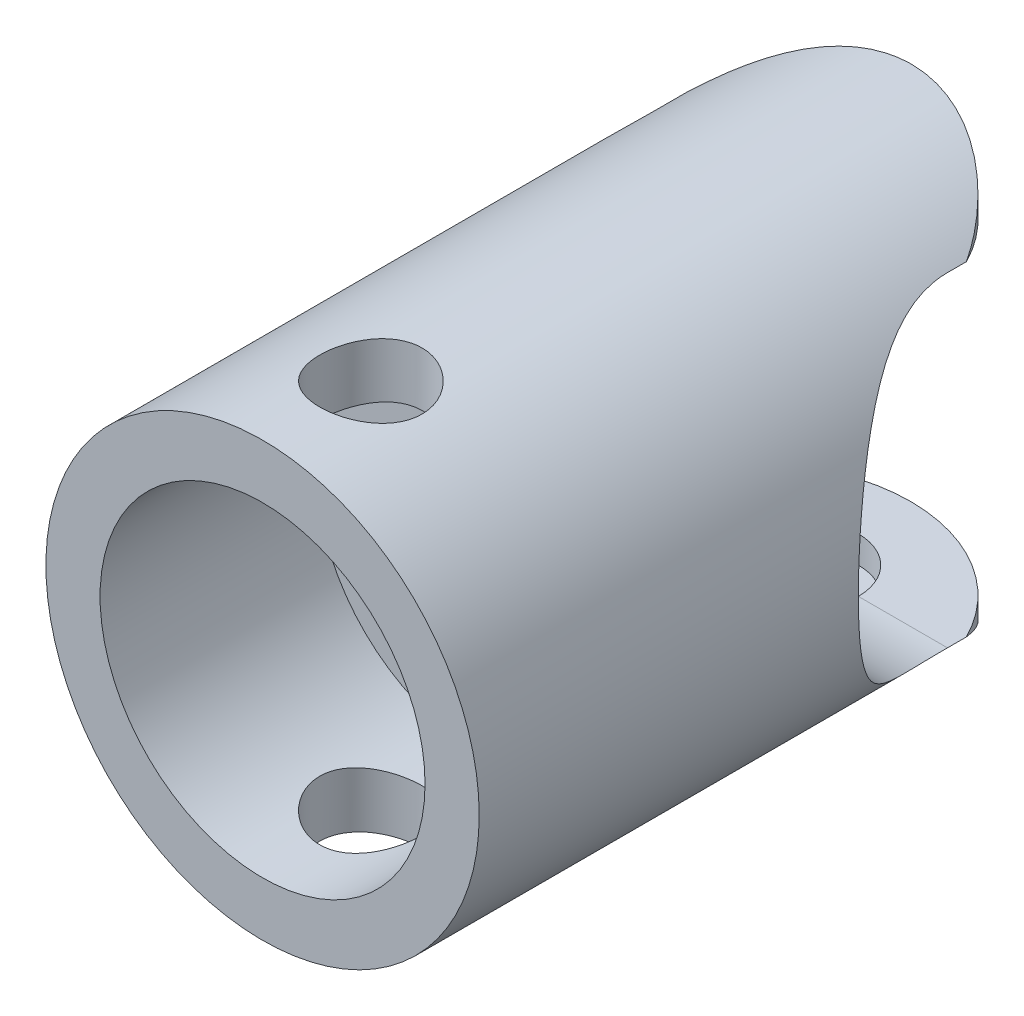
SolidWorks part; units mm, degrees
ref_plane "Front Plane" through (0, 0, 0) normal (0, 0, 1) x (1, 0, 0)
ref_plane "Top Plane" through (0, 0, 0) normal (0, 1, 0) x (1, 0, 0)
ref_plane "Right Plane" through (0, 0, 0) normal (1, 0, 0) x (0, 0, -1)
sketch "Sketch1" plane through (0, 0, 0) normal (0, 0, 1) x (1, 0, 0)
  circle A0 centre (0, 0) radius 12.7
extrude "Boss-Extrude1" add sketch "Sketch1" along normal blind 38.1
ref_plane "Plane1" through (12.7, 0, 0) normal (1, 0, 0) x (0, 0, -1)
sketch "Sketch2" plane through (12.7, 0, 0) normal (1, 0, 0) x (0, 0, -1)
  line L0 (0, 0) -> (-6.35, 0) construction
  line L1 (-6.35, 9.525) -> (3.175, 9.525)
  line L2 (3.175, 9.525) -> (3.175, 0)
  line L3 (3.175, 0) -> (3.175, -9.525)
  line L4 (3.175, -9.525) -> (-6.35, -9.525)
  circle A0 centre (-6.35, 0) radius 9.525
extrude "Cut-Extrude2" cut sketch "Sketch2" against normal through all contours A0 L2 L1 | A0 L4 L3 | A0 region at (12.7, 7.3974, -1.0474) region at (12.7, 0, 6.35) region at (12.7, -7.3974, -1.0474)
ref_plane "Plane2" through (0, -12.7, 0) normal (0, -1, 0) x (-1, 0, 0)
sketch "Sketch3" plane through (0, -12.7, 0) normal (0, -1, 0) x (-1, 0, 0)
  line L0 (0, 0) -> (8.4003, 0)
  line L1 (8.4003, 0) -> (8.4003, -4.839)
  line L2 (8.4003, 0) -> (8.4003, -6.35) construction
  line L3 (0, 0) -> (-8.4003, 0)
  line L4 (-8.4003, 0) -> (-8.4003, -5.2412)
  line L5 (-8.4003, -6.35) -> (-8.4003, 0) construction
  circle A0 centre (0.1074, -9.5244) radius 9.525
extrude "Cut-Extrude3" cut sketch "Sketch3" against normal blind 38.1 contours A0 L3 L4 | A0 L1 L0 region at (6.4082, -12.7, 1.4547) region at (-6.4476, -12.7, 1.3557)
sketch "Sketch4" plane through (0, 0, 38.1) normal (0, 0, 1) x (1, 0, 0)
  circle A0 centre (0, 0) radius 9.525
extrude "Cut-Extrude4" cut sketch "Sketch4" against normal blind 12.7
sketch "Sketch6" plane through (0, 0, 0) normal (0, 1, 0) x (1, 0, 0)
  line L0 (0, 0) -> (0, -6.35) construction
  circle A0 centre (0, -6.35) radius 3.175
extrude "Cut-Extrude5" cut sketch "Sketch6" against normal blind 11.1125 and the other way blind 11.1125
ref_plane "Plane3" through (0, -12.7, 0) normal (0, -1, 0) x (-1, 0, 0)
sketch "Sketch7" plane through (0, -12.7, 0) normal (0, -1, 0) x (-1, 0, 0)
  line L0 (0, -38.1) -> (0, -31.75) construction
  line L1 (-12.7, -38.1) -> (12.7, -38.1) construction
  circle A0 centre (0, -31.75) radius 3
extrude "Cut-Extrude6" cut sketch "Sketch7" against normal through all
